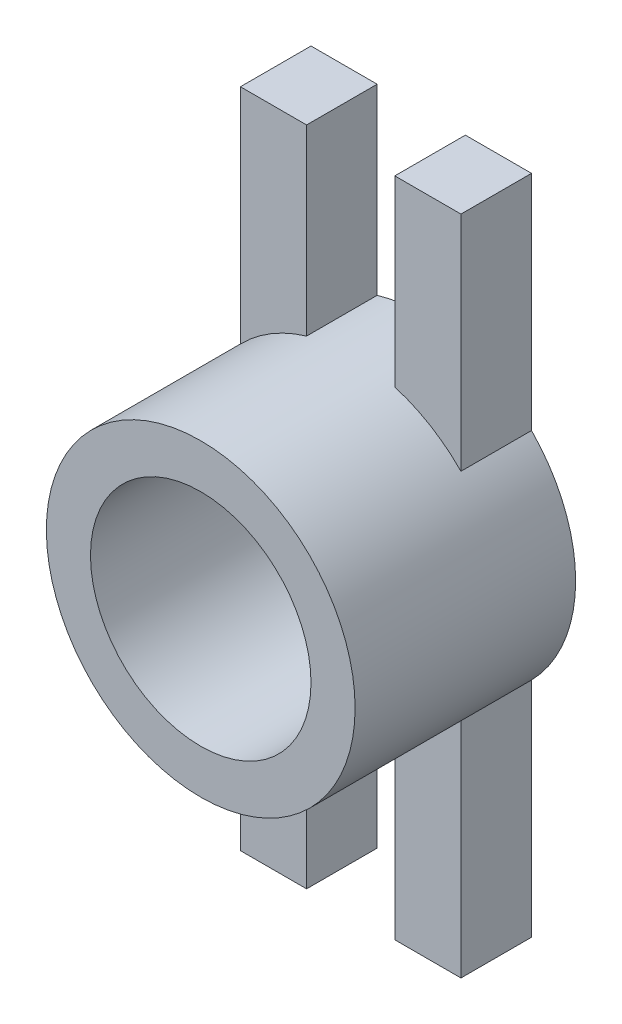
SolidWorks part; units mm, degrees
ref_plane "Front Plane" through (0, 0, 0) normal (1, 0, 0) x (0, 1, 0)
ref_plane "Top Plane" through (0, 0, 0) normal (0, 0, 1) x (0, 1, 0)
ref_plane "Right Plane" through (0, 0, 0) normal (0, 1, 0) x (-1, 0, 0)
sketch "Sketch1" plane through (0, 0, 0) normal (0, 0, 1) x (0, 1, 0)
  line L0 (0, 99.0826) -> (0, -105.4968) construction
  line L1 (-148.5394, 0) -> (143.138, 0) construction
  line L2 (-75, -10) -> (-75, -25)
  line L3 (-75, 25) -> (-24.4949, 25)
  line L4 (-75, 25) -> (-75, 10)
  line L5 (-75, -25) -> (-24.4949, -25)
  line L6 (75, 25) -> (75, 10)
  line L7 (-75, 25) -> (-33.2039, 11.068) construction
  line L8 (-75, -25) -> (75, 25) construction
  line L9 (-75, 10) -> (-33.541, 10)
  line L11 (-75, -10) -> (-33.541, -10)
  line L13 (-75, 10) -> (75, -10) construction
  line L14 (-75, -10) -> (75, 10) construction
  line L15 (75, -10) -> (75, -25)
  line L16 (24.4949, 25) -> (75, 25)
  line L17 (33.541, 10) -> (75, 10)
  line L18 (-23.7171, 7.9057) -> (75, -25) construction
  line L19 (33.541, -10) -> (75, -10)
  line L20 (24.4949, -25) -> (75, -25)
  circle A0 centre (0, 0) radius 35
  circle A1 centre (0, 0) radius 25
  dimension "D3" = 70
  dimension "D4" = 50
  dimension "D1" = 50
  dimension "D2" = 150
  dimension "D5" = 15
extrude "Boss-Extrude1" add sketch "Sketch1" along normal blind 50 contours A0 A1 region at (0, -34.0101, 0)
extrude "Boss-Extrude2" add sketch "Sketch1<3>" along normal blind 16 contours A0 L17 L6 L16 | A0 L20 L15 L19 | A0 L11 L2 L5 | A0 L3 L4 L9 region at (17.7462, -52.3693, 0) region at (-17.7462, -52.3693, 0) region at (17.7462, 52.3693, 0) region at (-17.7462, 52.3693, 0)
sketch "Sketch1<3>" plane through (0, 0, 0) normal (0, 0, 1) x (0, 1, 0) same geometry as "Sketch1"
